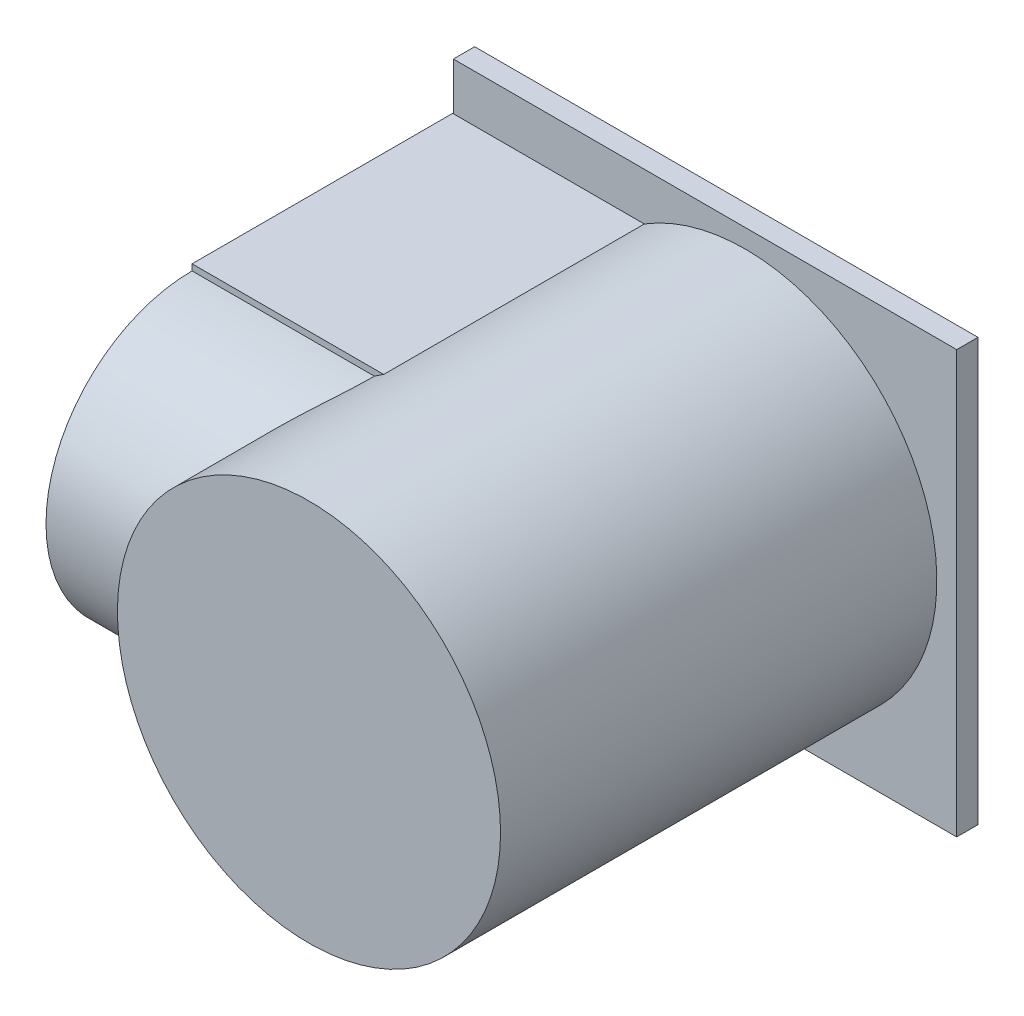
SolidWorks part; units mm, degrees
ref_plane "Front Plane" through (0, 0, 0) normal (0, 0, 1) x (1, 0, 0)
ref_plane "Top Plane" through (0, 0, 0) normal (0, 1, 0) x (1, 0, 0)
ref_plane "Right Plane" through (0, 0, 0) normal (1, 0, 0) x (0, 0, -1)
sketch "Sketch1" plane through (0, 0, 0) normal (0, 0, 1) x (1, 0, 0)
  line L1 (0.0397, 0.0395) -> (-0.0549, 0.0395)
  line L2 (0.0397, 0.0395) -> (0.0397, -0.0398)
  line L3 (0.0397, -0.0398) -> (-0.0549, -0.0398)
  line L4 (-0.0549, 0.0395) -> (-0.0549, -0.0398)
  circle A0 centre (0, 0) radius 0.036
extrude "Boss-Extrude1" add sketch "Sketch1" along normal blind 0.004
extrude "Boss-Extrude2" add sketch "Sketch1<2>" along normal blind 0.086 contours A0
sketch "Sketch1<2>" plane through (0, 0, 0) normal (0, 0, 1) x (1, 0, 0) same geometry as "Sketch1"
sketch "Sketch2" plane through (0, 0, 0) normal (1, 0, 0) x (0, 0, -1)
  line L0 (-0.053, -0.0255) -> (-0.053, -0.0266)
  line L1 (0, 0.0306) -> (-0.053, 0.0306)
  line L2 (0, 0.0306) -> (0, -0.0266)
  line L3 (0, -0.0266) -> (-0.053, -0.0266)
  line L4 (-0.053, 0.0306) -> (-0.053, 0.0294)
  arc A0 (-0.053, 0.0294) -> (-0.053, -0.0255) centre (-0.053, 0.002) ccw
extrude "Boss-Extrude3" add sketch "Sketch2" against normal blind 0.055
